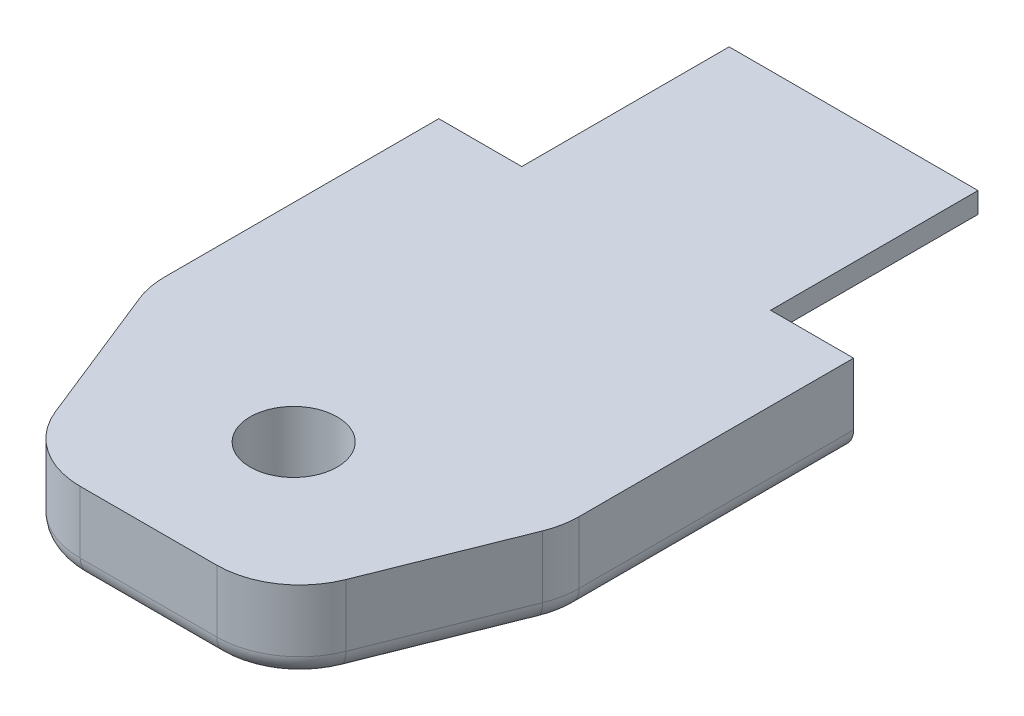
SolidWorks part; units mm, degrees
ref_plane "Plan de face" through (0, 0, 0) normal (0, 0, 1) x (1, 0, 0)
ref_plane "Plan de dessus" through (0, 0, 0) normal (0, 1, 0) x (1, 0, 0)
ref_plane "Plan de droite" through (0, 0, 0) normal (1, 0, 0) x (0, 0, -1)
sketch "Esquisse1" plane through (0, 0, 0) normal (0, 0, 1) x (1, 0, 0)
  line L0 (-3, 0) -> (3, 0)
  line L1 (3, 0) -> (6, 3)
  line L2 (6, 3) -> (6, 4)
  line L3 (6, 4) -> (-6, 4)
  line L4 (-6, 4) -> (-6, 3)
  line L5 (-6, 3) -> (-3, 0)
  dimension "D1" = 3
  dimension "D2" = 3
  dimension "D3" = 3
  dimension "D4" = 3
  dimension "D5" = 6
  dimension "D6" = 12
  dimension "D7" = 4
extrude "Boss.-Extru.1" add sketch "Esquisse1" along normal blind 10
sketch "Esquisse2" plane through (0, 0, 10) normal (0, 0, 1) x (1, 0, 0)
  line L0 (-3, 0) -> (3, 0) construction
  line L1 (-10, 0) -> (10, 0)
  line L2 (-10, 0) -> (-10, 4)
  line L3 (-10, 4) -> (10, 4)
  line L4 (10, 0) -> (10, 4)
  dimension "D1" = 20
  dimension "D2" = 10
  dimension "D3" = 4
extrude "Boss.-Extru.2" add sketch "Esquisse2" along normal blind 24
sketch "Esquisse3" plane through (0, 0, 0) normal (0, -1, 0) x (1, 0, 0)
  line L0 (0, 0) -> (0, 34) construction
  line L1 (-10, 34) -> (10, 34) construction
  circle A1 centre (0, 27) radius 2.1
  dimension "D2" = 4.2
  dimension "D3" = 7
extrude "Enlèv. mat.-Extru.1" cut sketch "Esquisse3" against normal through all
chamfer "Chanfrein1" distance 10 distance2 4 2 edges at (10, 2, 34) (-10, 2, 34) first distance on face at (10, 2, 22) first distance on face at (-10, 2, 22)
fillet "Congé1" radius 4 4 edges at (-10, 2, 24) (-6, 2, 34) (10, 2, 24) (6, 2, 34)
fillet "Congé2" radius 1 9 edges at (10, 0, 16.6148) (9.9278, 0, 23.9861) (8.3598, 0, 28.1004) (5.5344, 0, 33.3123) (0, 0, 34) (-5.5344, 0, 33.3123) (-8.3598, 0, 28.1004) (-9.9278, 0, 23.9861) (-10, 0, 16.6148)
